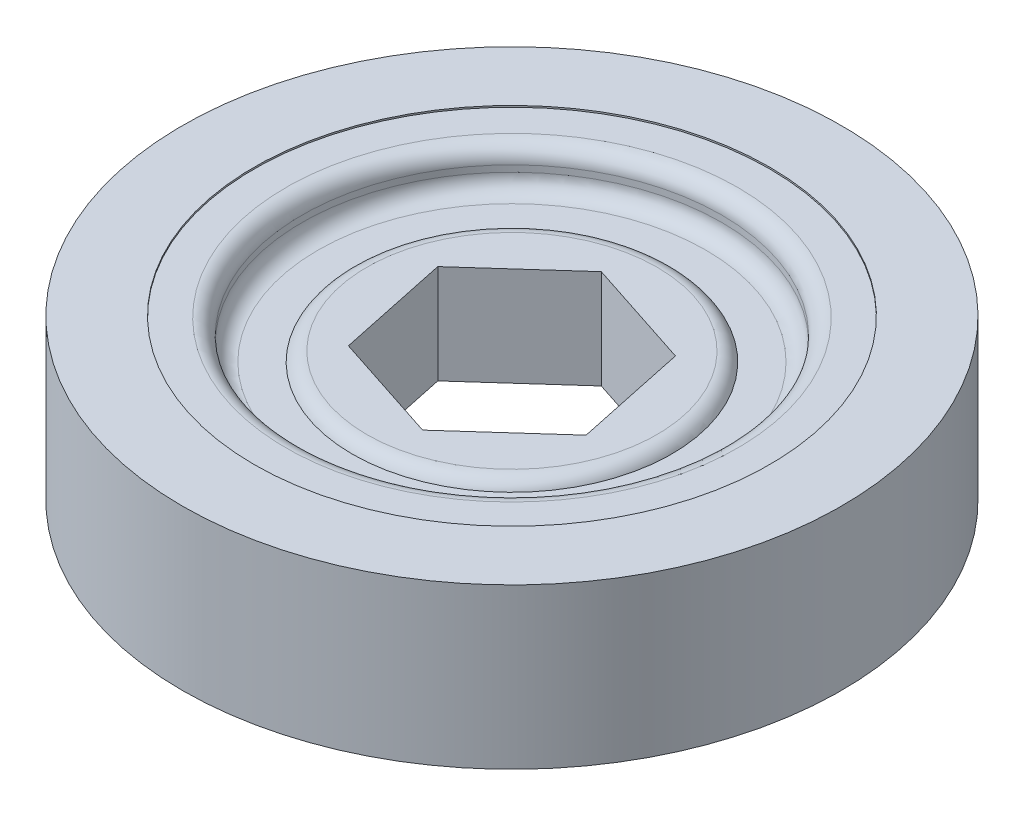
SolidWorks part; units mm, degrees
ref_plane "Front Plane" through (0, 0, 0) normal (0, 0, 1) x (1, 0, 0)
ref_plane "Top Plane" through (0, 0, 0) normal (0, 1, 0) x (1, 0, 0)
ref_plane "Right Plane" through (0, 0, 0) normal (1, 0, 0) x (0, 0, -1)
sketch "Sketch1" plane through (0, 0, 0) normal (0, 0, 1) x (1, 0, 0)
  line L0 (-10.3187, 0) -> (10.3187, 0) construction
  line L1 (10.3187, -5) -> (10.3187, 5)
  line L2 (10.3187, 5) -> (5.8188, 5)
  line L3 (2.8188, 4.9) -> (2.8188, 2.5)
  line L4 (2.8188, 2.5) -> (-0.3187, 2.5)
  line L5 (-0.3187, 2.5) -> (-0.3187, 3.1)
  line L6 (-0.3187, 3.1) -> (-10.3187, 3.1)
  line L7 (-10.3187, 3.1) -> (-10.3187, -3.1)
  line L8 (5.8188, -4.9) -> (2.8188, -4.9)
  line L9 (5.8188, -5) -> (5.8188, -4.9)
  line L10 (-0.3187, -3.1) -> (-10.3187, -3.1)
  line L11 (-0.3187, -2.5) -> (-0.3187, -3.1)
  line L12 (2.8188, -2.5) -> (-0.3187, -2.5)
  line L13 (5.8188, 5) -> (5.8188, 4.9)
  line L14 (5.8188, 4.9) -> (2.8188, 4.9)
  line L15 (2.8188, -4.9) -> (2.8188, -2.5)
  line L16 (10.3187, -5) -> (5.8188, -5)
  point P2 (0, 0)
  dimension "D1" = 20.6375
  dimension "D2" = 5
  dimension "D3" = 2.5
  dimension "D4" = 1.8
  dimension "D5" = 10
  dimension "D6" = 7.5
  dimension "D7" = 0.1
  dimension "D8" = 4.5
revolve "Revolve1" add sketch "Sketch1" angle 360 about L7
sketch "Sketch4" plane through (0, 3.1, 0) normal (0, 1, 0) x (1, 0, 0)
  line L1 (-17.2111, 2.2489) -> (-15.7125, -4.8445)
  line L2 (-15.7125, -4.8445) -> (-8.8201, -7.0934)
  line L3 (-8.8201, -7.0934) -> (-3.4264, -2.2489)
  line L4 (-3.4264, -2.2489) -> (-4.925, 4.8445)
  line L5 (-4.925, 4.8445) -> (-11.8174, 7.0934)
  line L6 (-11.8174, 7.0934) -> (-17.2111, 2.2489)
  circle A0 centre (-10.3187, 0) radius 6.2787 construction
  dimension "D1" = 14.5
extrude "Cut-Extrude2" cut sketch "Sketch4" against normal through all
fillet "Fillet1" radius 1 1 edges at (-10.3187, 3.1, 10)
fillet "Fillet2" radius 1 1 edges at (-10.3187, 4.9, 13.1375)
fillet "Fillet3" radius 1 1 edges at (-10.3187, 2.5, 13.1375)
fillet "Fillet4" radius 1 2 edges at (-10.3187, -2.5, 10) (-10.3187, -2.5, 13.1375)
fillet "Fillet5" radius 1 1 edges at (-10.3187, -4.9, 13.1375)
